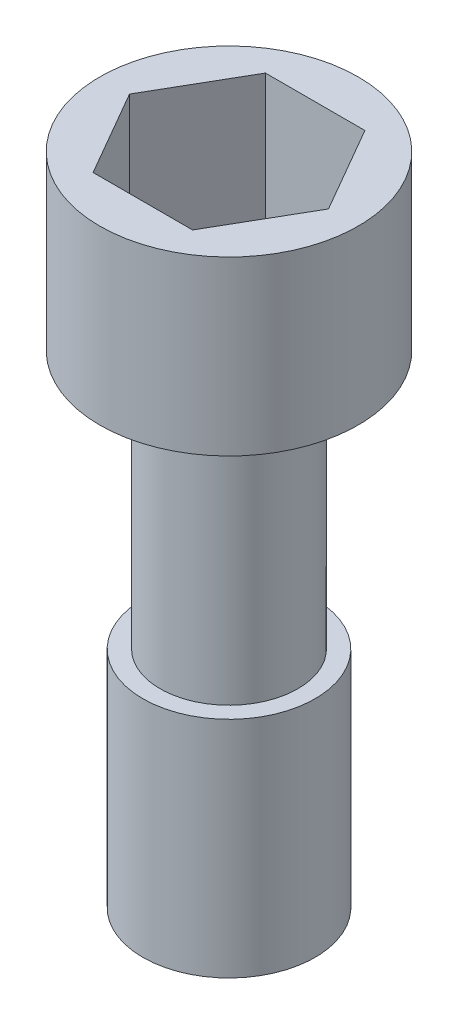
SolidWorks part; units mm, degrees
ref_plane "Front Plane" through (0, 0, 0) normal (0, 0, 1) x (1, 0, 0)
ref_plane "Top Plane" through (0, 0, 0) normal (0, 1, 0) x (1, 0, 0)
ref_plane "Right Plane" through (0, 0, 0) normal (1, 0, 0) x (0, 0, -1)
sketch "Sketch1" plane through (0, 0, 0) normal (0, 1, 0) x (1, 0, 0)
  line L1 (5.7735, 0) -> (2.8868, 5)
  line L2 (2.8868, 5) -> (-2.8868, 5)
  line L3 (-2.8868, 5) -> (-5.7735, 0)
  line L4 (-5.7735, 0) -> (-2.8868, -5)
  line L5 (-2.8868, -5) -> (2.8868, -5)
  line L6 (2.8868, -5) -> (5.7735, 0)
  circle A0 centre (0, 0) radius 7.5
  circle A1 centre (0, 0) radius 5 construction
  dimension "D1" = 15
  dimension "D2" = 10
extrude "Boss-Extrude1" add sketch "Sketch1" along normal blind 8
sketch "Sketch2" plane through (0, 0, 0) normal (0, -1, 0) x (1, 0, 0)
  circle A0 centre (0, 0) radius 4
  circle A1 centre (0, 0) radius 7.5
  circle A2 centre (0, 0) radius 7.5
  circle M3 centre (0, 0) radius 7.5
  line M4 (2.8868, 5) -> (5.7735, 0)
  line M5 (5.7735, 0) -> (2.8868, -5)
  line M6 (2.8868, -5) -> (-2.8868, -5)
  line M7 (-2.8868, -5) -> (-5.7735, 0)
  line M8 (-5.7735, 0) -> (-2.8868, 5)
  line M9 (-2.8868, 5) -> (2.8868, 5)
  dimension "D1" = 0
  dimension "D2" = 3.5
extrude "Boss-Extrude2" add sketch "Sketch2" along normal blind 2 contours A0 | M3 M9 M4 M5 M6 M7 M8 | A0 M4 M9 M8 M7 M6 M5 | A0 | A2 region at (0, 0, 0) region at (-7.2879, 0, 0) region at (4.1978, 0, 2.4236)
extrude "Boss-Extrude3" add sketch "Sketch2<3>" along normal blind 17 contours A0 region at (0, 0, 0)
sketch "Sketch2<3>" plane through (0, 0, 0) normal (0, -1, 0) x (1, 0, 0) same geometry as "Sketch2"
sketch "Sketch3" plane through (0, -17, 0) normal (0, -1, 0) x (1, 0, 0)
  circle A2 centre (0, 0) radius 5
  circle A3 centre (0, 0) radius 5
  dimension "D1" = 1
extrude "Boss-Extrude4" add sketch "Sketch3" along normal blind 13
